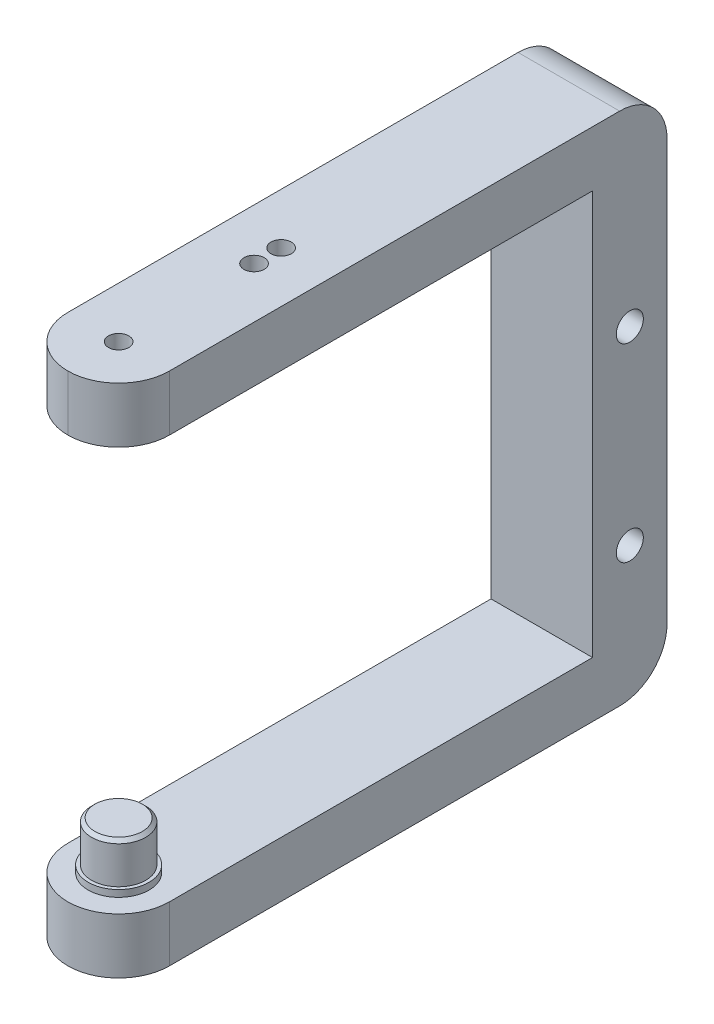
SolidWorks part; units mm, degrees
ref_plane "Piano frontale" through (0, 0, 0) normal (0, 0, 1) x (1, 0, 0)
ref_plane "Piano superiore" through (0, 0, 0) normal (0, 1, 0) x (1, 0, 0)
ref_plane "Piano destro" through (0, 0, 0) normal (1, 0, 0) x (0, 0, -1)
sketch "Schizzo1" plane through (0, 0, 0) normal (0, 0, 1) x (1, 0, 0)
  line L0 (0, 0) -> (15, 0)
  line L1 (15, 0) -> (15, 76.1)
  line L2 (15, 76.1) -> (0, 76.1)
  line L3 (0, 76.1) -> (0, 0)
  dimension "D1" = 15
  dimension "D2" = 76.1
extrude "Estrusione-Estrusione1" add sketch "Schizzo1" along normal blind 11
sketch "Schizzo2" plane through (0, 0, 11) normal (0, 0, 1) x (1, 0, 0)
  line L0 (15, 0) -> (15, 8.2)
  line L1 (15, 0) -> (15, 76.1) construction
  line L2 (15, 8.2) -> (0, 8.2)
  line L3 (0, 76.1) -> (0, 0) construction
  line L4 (0, 8.2) -> (0, 0)
  line L5 (0, 0) -> (15, 0)
  dimension "D1" = 8.2
extrude "Estrusione-Estrusione2" add sketch "Schizzo2" along normal blind 62.5
sketch "Schizzo3" plane through (0, 8.2, 0) normal (0, 1, 0) x (1, 0, 0)
  line L0 (15, -73.5) -> (0, -73.5) construction
  circle A0 centre (7.5, -73.5) radius 7.5
extrude "Estrusione-Estrusione3" add sketch "Schizzo3" against normal blind 8.2
sketch "Schizzo4" plane through (0, 8.2, 0) normal (0, 1, 0) x (1, 0, 0)
  circle A0 centre (7.5, -73.5) radius 4
extrude "Estrusione-Estrusione4" add sketch "Schizzo4" along normal blind 7
chamfer "Smusso1" distance 0.5 angle 45 1 edges at (7.5, 15.2, 77.5)
sketch "Schizzo5" plane through (0, 0, 11) normal (0, 0, 1) x (1, 0, 0)
  line L0 (15, 76.1) -> (15, 67.9)
  line L1 (15, 8.2) -> (15, 76.1) construction
  line L2 (15, 67.9) -> (0, 67.9)
  line L3 (0, 76.1) -> (0, 8.2) construction
  line L4 (0, 67.9) -> (0, 76.1)
  line L5 (0, 76.1) -> (15, 76.1)
  dimension "D1" = 8.2
extrude "Estrusione-Estrusione5" add sketch "Schizzo5" along normal blind 70
hole_wizard "Ø3.0 (3) Diameter Hole1" positions "Schizzo6" profile "Schizzo8" hole size "Ø3.0" standard "ISO"
sketch "Schizzo6" plane through (0, 76.1, 0) normal (0, 1, 0) x (1, 0, 0)
  line L1 (15, -81) -> (15, 0) construction
  line L2 (0, -81) -> (0, 0) construction
  circle A1 centre (7.5, -73.5) radius 3.5 construction
  point P0 (7.5, -49.5)
  point P2 (7.5, -53.5)
  dimension "D1" = 4
  dimension "D2" = 20
  dimension "D3" = 7.5
  dimension "D4" = 7.5
sketch "Schizzo8" plane through (7.5, 76.1, 49.5) normal (1, 0, 0) x (0, 0, 1)
  line L0 (0, 0) -> (0, 10.9013)
  line L1 (0, 10.9013) -> (1.5, 10)
  line L2 (1.5, 10) -> (1.5, 0)
  line L5 (1.5, 0) -> (0, 0)
  line L10 (0, 10.9013) -> (-1.5, 10) construction
  line L11 (0, -6.35) -> (0, 107.95) construction
  dimension "Hole Dia." = 3
  dimension "Hole Depth" = 10
  dimension "Drill Angle" = 118
fillet "Raccordo1" radius 7.5 2 edges at (15, 72, 81) (0, 72, 81)
fillet "Raccordo2" radius 7 2 edges at (7.5, 0, 0) (7.5, 76.1, 0)
hole_wizard "Ø4.0 (4) Diameter Hole1" positions "Schizzo10" profile "Schizzo11" hole size "Ø4.0" standard "ISO" end condition through all
sketch "Schizzo10" plane through (15, 0, 0) normal (1, 0, 0) x (0, 0, -1)
  line L0 (-73.5, 0) -> (-7, 0) construction
  line L1 (0, 7) -> (0, 69.1) construction
  point P0 (-5.5, 19.8)
  point P7 (-5.5, 47.8)
  dimension "D1" = 19.8
  dimension "D2" = 5.5
  dimension "D3" = 5.5
  dimension "D4" = 28
sketch "Schizzo11" plane through (15, 19.8, 5.5) normal (0, 1, 0) x (0, 0, -1)
  line L0 (0, 0) -> (0, 15)
  line L1 (0, 15) -> (2, 15)
  line L2 (2, 15) -> (2, 0)
  line L5 (2, 0) -> (0, 0)
  line L11 (0, -6.35) -> (0, 107.95) construction
  dimension "Thru Hole Dia." = 4
  dimension "Thru Hole Depth" = 15
sketch "Schizzo12" plane through (0, 8.2, 0) normal (0, 1, 0) x (1, 0, 0)
  circle A0 centre (7.5, -73.5) radius 4.5
extrude "Estrusione-Estrusione6" add sketch "Schizzo12" along normal blind 1
hole_wizard "Ø3.0 (3) Diameter Hole2" positions "Sketch1" profile "Sketch2" hole size "Ø3.0" standard "ISO" end condition up to next
sketch "Sketch1" plane through (0, 76.1, 0) normal (0, 1, 0) x (1, 0, 0)
  point P0 (7.5, -73.5)
sketch "Sketch2" plane through (7.5, 76.1, 73.5) normal (1, 0, 0) x (0, 0, 1)
  line L0 (0, 0) -> (0, 8.2)
  line L1 (0, 8.2) -> (1.5, 8.2)
  line L2 (1.5, 8.2) -> (1.5, 0)
  line L5 (1.5, 0) -> (0, 0)
  line L11 (0, -6.35) -> (0, 107.95) construction
  dimension "Thru Hole Dia." = 3
  dimension "Thru Hole Depth" = 8.2
